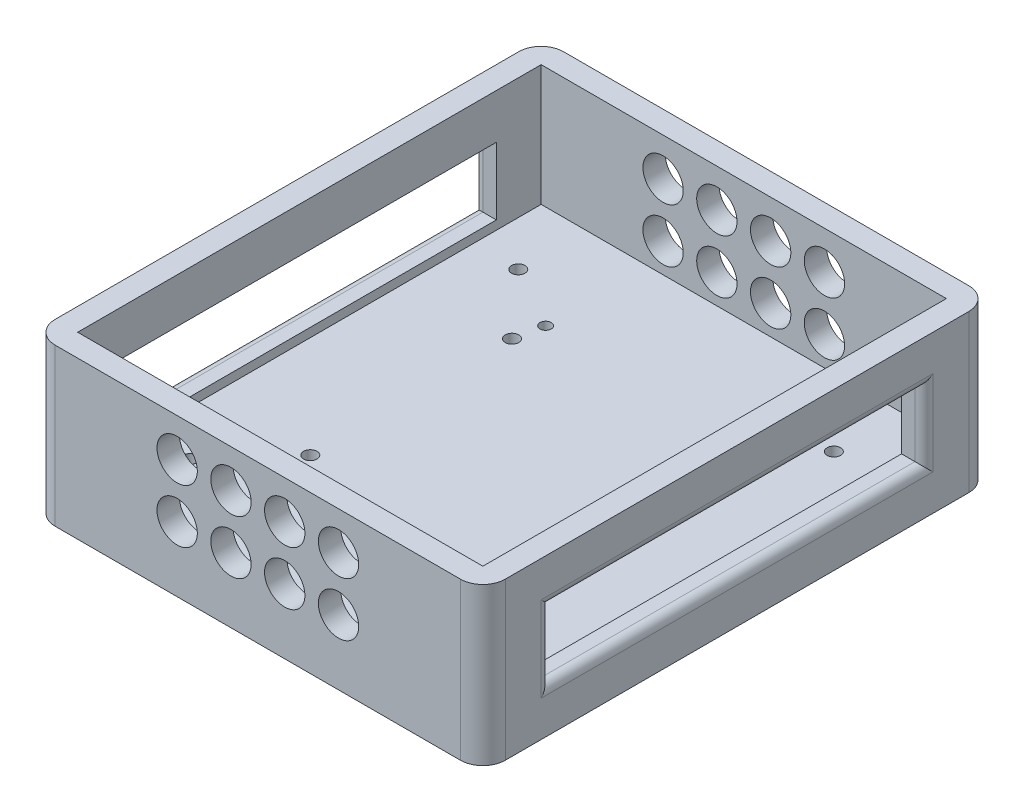
SolidWorks part; units mm, degrees
ref_plane "Front Plane" through (0, 0, 0) normal (0, 0, 1) x (1, 0, 0)
ref_plane "Top Plane" through (0, 0, 0) normal (0, 1, 0) x (1, 0, 0)
ref_plane "Right Plane" through (0, 0, 0) normal (1, 0, 0) x (0, 0, -1)
sketch "Sketch1" plane through (0, 0, 0) normal (0, 1, 0) x (1, 0, 0)
  line L1 (-50.2, -56.7) -> (50.2, -56.7)
  line L2 (-50.2, -56.7) -> (-50.2, 56.7)
  line L3 (-50.2, 56.7) -> (50.2, 56.7)
  line L4 (50.2, -56.7) -> (50.2, 56.7)
  line L5 (-50.2, -56.7) -> (50.2, 56.7) construction
  line L6 (-50.2, 56.7) -> (50.2, -56.7) construction
  point P0 (0, 0)
  dimension "D1" = 100.4
  dimension "D2" = 113.4
extrude "Boss-Extrude2" add sketch "Sketch1" along normal blind 35 contours L3 L4 L1 L2
sketch "Sketch2" plane through (0, 35, 0) normal (0, 1, 0) x (1, 0, 0)
  line L1 (-45.2, -51.7) -> (45.2, -51.7)
  line L2 (-45.2, -51.7) -> (-45.2, 51.7)
  line L3 (-45.2, 51.7) -> (45.2, 51.7)
  line L4 (45.2, -51.7) -> (45.2, 51.7)
  line L5 (-45.2, -51.7) -> (45.2, 51.7) construction
  line L6 (-45.2, 51.7) -> (45.2, -51.7) construction
  point P0 (0, 0)
  dimension "D1" = 103.4
  dimension "D2" = 90.4
extrude "Cut-Extrude1" cut sketch "Sketch2" against normal blind 27
fillet "Fillet4" radius 5 4 edges at (50.2, 17.5, -56.7) (-50.2, 17.5, -56.7) (-50.2, 17.5, 56.7) (50.2, 17.5, 56.7)
sketch "Sketch3" plane through (0, 0, -56.7) normal (0, 0, -1) x (-1, 0, 0)
  line L0 (45.2, 0) -> (-45.2, 0) construction
  line L1 (-50.2, 0) -> (-50.2, 35) construction
  circle A0 centre (-18, 14.5) radius 4.5
  dimension "D1" = 14.5
  dimension "D3" = 9
  dimension "D2" = 32.2
sketch "Sketch4" plane through (50.2, 0, 0) normal (1, 0, 0) x (0, 0, -1)
  line L0 (-56.7, 0) -> (-56.7, 35) construction
  line L1 (-41.7, 25) -> (41.7, 25)
  line L2 (-41.7, 25) -> (-41.7, 10)
  line L3 (-41.7, 10) -> (41.7, 10)
  line L4 (41.7, 25) -> (41.7, 10)
  line L6 (-51.7, 0) -> (51.7, 0) construction
  dimension "D1" = 83.4
  dimension "D2" = 15
  dimension "D3" = 10
  dimension "D4" = 15
extrude "Cut-Extrude3" cut sketch "Sketch4" against normal blind 123
fillet "Fillet5" radius 2 4 edges at (50.2, 17.5, 41.7) (50.2, 25, 0) (50.2, 17.5, -41.7) (50.2, 10, 0)
fillet "Fillet6" radius 2 4 edges at (-50.2, 17.5, 41.7) (-50.2, 25, 0) (-50.2, 17.5, -41.7) (-50.2, 10, 0)
extrude "Cut-Extrude4" cut sketch "Sketch3" against normal blind 123 contours A0
sketch "Sketch5" plane through (0, 8, 0) normal (0, 1, 0) x (1, 0, 0)
  line L0 (-50.2, -51.7) -> (-50.2, 51.7) construction
  line L1 (-45.2, -56.7) -> (45.2, -56.7) construction
  circle A0 centre (-22.5, 22.5) radius 1.5
  circle A1 centre (22.5, 22.5) radius 1.5
  circle A2 centre (-22.5, -22.5) radius 1.5
  circle A3 centre (22.5, -22.5) radius 1.5
  dimension "D1" = 45
  dimension "D2" = 45
  dimension "D3" = 45
  dimension "D4" = 45
  dimension "D5" = 27.7
  dimension "D6" = 34.2
extrude "Cut-Extrude5" cut sketch "Sketch5" against normal blind 37
sketch "Sketch6" plane through (0, 0, 0) normal (0, -1, 0) x (1, 0, 0)
  circle A0 centre (-22.5, 22.5) radius 3
  circle A1 centre (-22.5, -22.5) radius 3
  circle A2 centre (22.5, 22.5) radius 3
  circle A3 centre (22.5, -22.5) radius 3
extrude "Cut-Extrude6" cut sketch "Sketch6" against normal blind 4
sketch "Sketch7" plane through (0, 0, 0) normal (0, -1, 0) x (1, 0, 0)
  line L0 (-45.2, 56.7) -> (45.2, 56.7) construction
  line L1 (50.2, 51.7) -> (50.2, -51.7) construction
  circle A0 centre (-21.25, 28.75) radius 1.25
  circle A1 centre (-21.25, -28.75) radius 1.25
  circle A2 centre (21.25, -28.75) radius 1.25
  circle A3 centre (21.25, 28.75) radius 1.25
  dimension "D1" = 42.5
  dimension "D2" = 42.5
  dimension "D3" = 57.5
  dimension "D4" = 57.5
  dimension "D5" = 27.95
  dimension "D6" = 28.95
  dimension "D7" = 28.95
extrude "Cut-Extrude7" cut sketch "Sketch7" against normal blind 17
sketch "Sketch8" plane through (0, 8, 0) normal (0, 1, 0) x (1, 0, 0)
  line L0 (-45.2, -56.7) -> (45.2, -56.7) construction
  line L1 (-50.2, -51.7) -> (-50.2, 51.7) construction
  circle A0 centre (-35.2, 36.6) radius 1.5
  circle A1 centre (35.2, 36.6) radius 1.5
  circle A2 centre (-35.2, -36.7) radius 1.5
  circle A3 centre (35.2, -36.7) radius 1.5
  dimension "D1" = 73.3
  dimension "D2" = 73.3
  dimension "D3" = 70.4
  dimension "D4" = 70.4
  dimension "D5" = 20
  dimension "D6" = 15
extrude "Cut-Extrude8" cut sketch "Sketch8" against normal blind 9
sketch "Sketch9" plane through (0, 0, 0) normal (0, -1, 0) x (1, 0, 0)
  circle A0 centre (-35.2, 36.7) radius 3
  circle A1 centre (35.2, 36.7) radius 3
  circle A2 centre (-35.2, -36.6) radius 3
  circle A3 centre (35.2, -36.6) radius 3
extrude "Cut-Extrude9" cut sketch "Sketch9" against normal blind 4
pattern_linear "LPattern2" count 4 spacing 12 along (-1, 0, 0) count 2 spacing 12 along (0, 1, 0) of "Cut-Extrude4"
